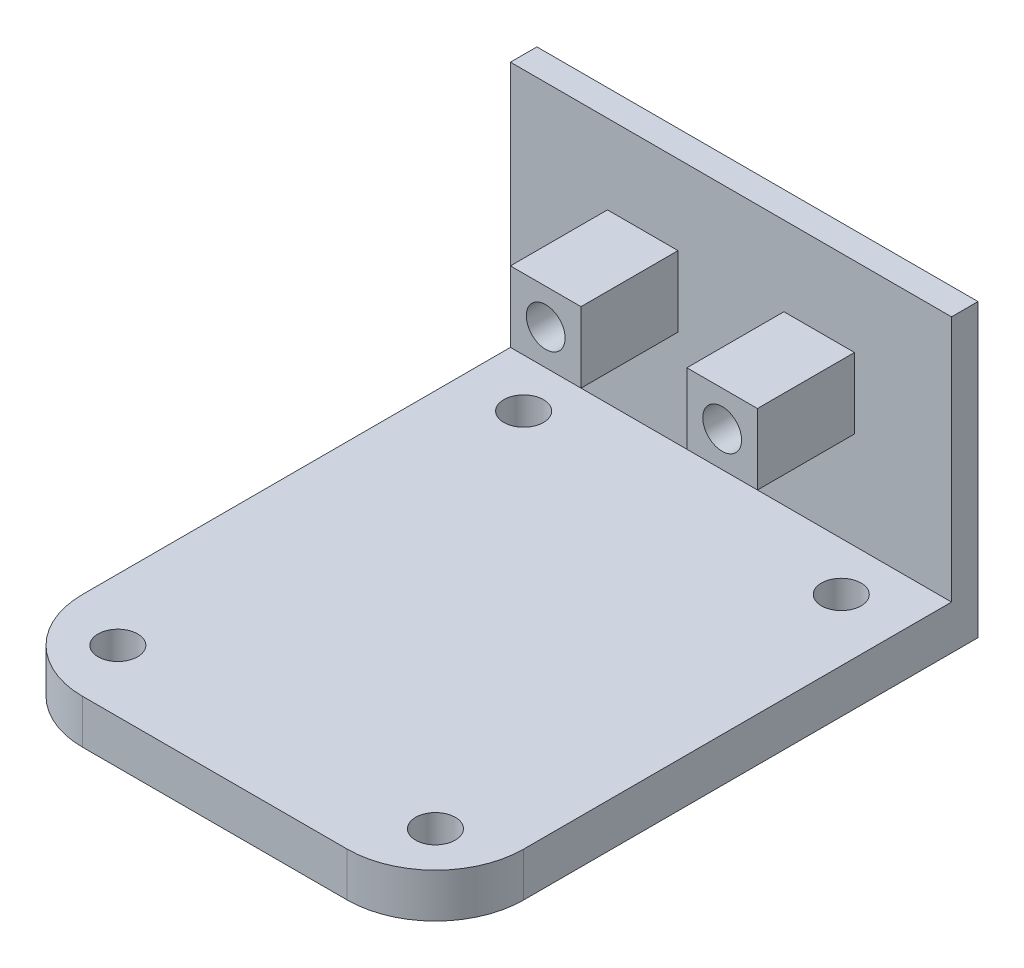
SolidWorks part; units mm, degrees
ref_plane "Front Plane" through (0, 0, 0) normal (0, 0, 1) x (1, 0, 0)
ref_plane "Top Plane" through (0, 0, 0) normal (0, 1, 0) x (1, 0, 0)
ref_plane "Right Plane" through (0, 0, 0) normal (1, 0, 0) x (0, 0, -1)
sketch "Sketch1" plane through (0, 0, 0) normal (0, 0, 1) x (1, 0, 0)
  line L1 (-25, 16.5) -> (25, 16.5)
  line L2 (-25, 16.5) -> (-25, -16.5)
  line L3 (-25, -16.5) -> (25, -16.5)
  line L4 (25, 16.5) -> (25, -16.5)
  line L5 (-25, 16.5) -> (25, -16.5) construction
  line L6 (-25, -16.5) -> (25, 16.5) construction
  point P0 (0, 0)
  dimension "D1" = 33
  dimension "D2" = 50
extrude "Boss-Extrude1" add sketch "Sketch1" along normal blind 3 contours L2 L3 L4 L1
sketch "Sketch2" plane through (0, 0, 3) normal (0, 0, 1) x (1, 0, 0)
  line L0 (25, 16.5) -> (25, -16.5) construction
  line L1 (-25, -16.5) -> (25, -16.5)
  line L2 (-25, -16.5) -> (-25, -11.5)
  line L3 (-25, -11.5) -> (25, -11.5)
  line L4 (25, -16.5) -> (25, -11.5)
  dimension "D1" = 5
extrude "Boss-Extrude2" add sketch "Sketch2" along normal blind 58.5
sketch "Sketch3" plane through (0, -11.5, 0) normal (0, 1, 0) x (1, 0, 0)
  line L0 (-25, -51.5) -> (-25, -61.5)
  line L1 (-25, -61.5) -> (-15, -61.5)
  line L2 (15, -61.5) -> (25, -61.5)
  line L3 (25, -61.5) -> (25, -51.5)
  arc A1 (15, -61.5) -> (25, -51.5) centre (15, -51.5) ccw construction
  arc A2 (15, -61.5) -> (25, -51.5) centre (15, -51.5) ccw
  arc A3 (-25, -51.5) -> (-15, -61.5) centre (-15, -51.5) ccw construction
  arc A4 (-25, -51.5) -> (-15, -61.5) centre (-15, -51.5) ccw
  circle A5 centre (-18, -54.5) radius 2.2479 construction
  circle A6 centre (-18, -54.5) radius 2.2479
  circle A7 centre (18, -54.5) radius 2.2479 construction
  circle A8 centre (18, -54.5) radius 2.2479
  circle A9 centre (-18, -8.5) radius 2.2479 construction
  circle A10 centre (-18, -8.5) radius 2.2479
  circle A11 centre (18, -8.5) radius 2.2479 construction
  circle A12 centre (18, -8.5) radius 2.2479
extrude "Cut-Extrude1" cut sketch "Sketch3" against normal up to surface (5 mm away) up to face at (0, -16.5, 30.75)
sketch "Sketch4" plane through (0, 0, 3) normal (0, 0, 1) x (1, 0, 0)
  line L5 (-14, 7.5) -> (-6, 7.5)
  line L6 (-14, 7.5) -> (-14, -0.5)
  line L7 (-14, -0.5) -> (-6, -0.5)
  line L8 (-6, 7.5) -> (-6, -0.5)
  line L9 (-14, 7.5) -> (-6, -0.5) construction
  line L10 (-14, -0.5) -> (-6, 7.5) construction
  line L11 (6, 7.5) -> (14, 7.5)
  line L12 (6, 7.5) -> (6, -0.5)
  line L13 (6, -0.5) -> (14, -0.5)
  line L14 (14, 7.5) -> (14, -0.5)
  line L15 (6, 7.5) -> (14, -0.5) construction
  line L16 (6, -0.5) -> (14, 7.5) construction
  circle A0 centre (-10, 3.5) radius 2.2 construction
  circle A1 centre (-10, 3.5) radius 2.2
  circle A2 centre (10, 3.5) radius 2.2 construction
  circle A3 centre (10, 3.5) radius 2.2
  dimension "D1" = 8
extrude "Boss-Extrude3" add sketch "Sketch4" along normal blind 11
sketch "Sketch5" plane through (0, 0, 14) normal (0, 0, 1) x (1, 0, 0)
  circle A0 centre (10, 3.5) radius 2.2 construction
  circle A1 centre (10, 3.5) radius 2.2
  circle A2 centre (-10, 3.5) radius 2.2 construction
  circle A3 centre (-10, 3.5) radius 2.2
extrude "Cut-Extrude2" cut sketch "Sketch5" against normal up to surface (14 mm away) up to face at (0, 0, 0)
